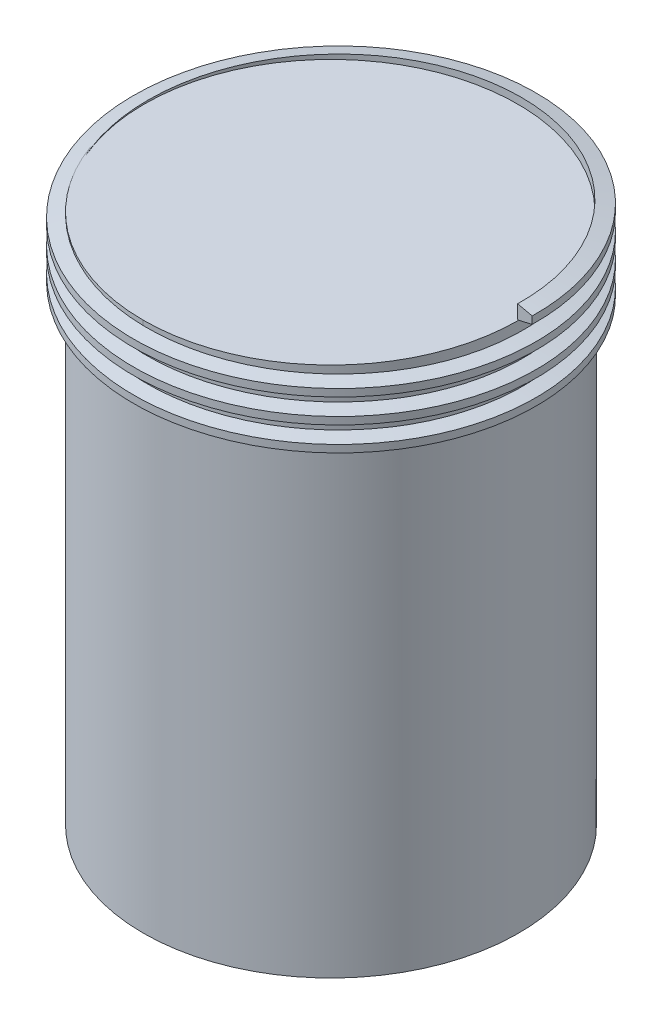
SolidWorks part; units mm, degrees
material "1060 Alloy"
ref_plane "Front Plane" through (0, 0, 0) normal (0, 0, 1) x (1, 0, 0)
ref_plane "Top Plane" through (0, 0, 0) normal (0, 1, 0) x (1, 0, 0)
ref_plane "Right Plane" through (0, 0, 0) normal (1, 0, 0) x (0, 0, -1)
sketch "Sketch1" plane through (0, 0, 0) normal (0, 1, 0) x (1, 0, 0)
  circle A0 centre (0, 0) radius 33.6
  dimension "D1" = 67.2
extrude "Boss-Extrude1" add sketch "Sketch1" against normal blind 95 contours A0
sketch "Sketch2" plane through (0, 0, 0) normal (0, 0, 1) x (1, 0, 0)
  line L0 (33.6, 2.2) -> (33.6, 0.2) construction
  line L1 (33.6, -95) -> (33.6, 0) construction
  line L2 (33.6, 0) -> (33.6, -15) construction
  line L3 (33.6, 1.2) -> (35.8, 1.2) construction
  line L4 (35.8, 1.7) -> (35.8, 0.7) construction
  line L5 (33.6, 0.2) -> (35.8, 0.7) construction
  line L6 (33.6, 2.2) -> (35.8, 1.7) construction
  line L7 (33.4, 2.4506) -> (33.4, -0.0506)
  line L8 (33.4, -0.0506) -> (36, 0.5404)
  line L9 (36, 1.8596) -> (36, 0.5404)
  line L10 (33.4, 2.4506) -> (36, 1.8596)
  dimension "D1" = 15
  dimension "D2" = 15.2
  dimension "D3" = 2
  dimension "D4" = 2.2
  dimension "D5" = 0.5
  dimension "D6" = 2.2561
  dimension "D7" = 0.2
ref_plane "Plane1" through (0, 1.2, 0) normal (0, 1, 0) x (1, 0, 0)
sketch "Sketch4" plane through (0, 1.2, 0) normal (0, 1, 0) x (1, 0, 0)
  circle A0 centre (0, 0) radius 33.6
  dimension "D1" = 67.2
curve "Helix/Spiral2" pitch 4.3333 height 15.1667 radius 33.6 left hand yes centre (0, 1.2, 0) axis (0, -1, 0) start towards (1, 0, 0)
sweep "Sweep1" add profiles "Sketch2" path "Helix/Spiral2"
ref_plane "Plane3" through (0, 0, 0) normal (0, 1, 0) x (1, 0, 0)
